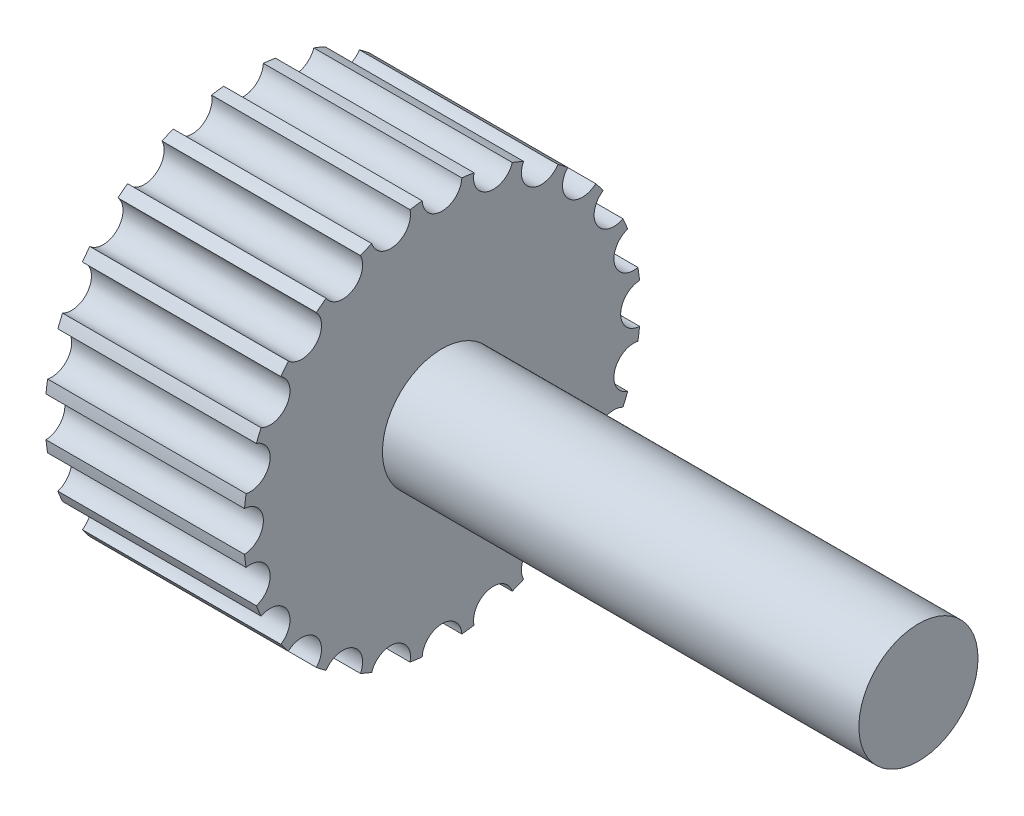
SolidWorks part; units mm, degrees
material "Brass"
ref_plane "Front Plane" through (0, 0, 0) normal (0, 0, 1) x (1, 0, 0)
ref_plane "Top Plane" through (0, 0, 0) normal (0, 1, 0) x (1, 0, 0)
ref_plane "Right Plane" through (0, 0, 0) normal (1, 0, 0) x (0, 0, -1)
sketch "Sketch1" plane through (0, 0, 0) normal (1, 0, 0) x (0, 0, -1)
  circle A0 centre (0, 0) radius 5
  dimension "D1" = 10
extrude "Boss-Extrude1" add sketch "Sketch1" along normal blind 5
sketch "Sketch2" plane through (0, 0, 0) normal (1, 0, 0) x (0, 0, -1)
  circle A0 centre (0, 0) radius 1.5
  dimension "D1" = 3
extrude "Boss-Extrude2" add sketch "Sketch2" along normal blind 17
cosmetic thread "Cosmetic Thread1" parameters "D1"=12, "D2"=0
sketch "Sketch3" plane through (0, 0, 0) normal (1, 0, 0) x (0, 0, -1)
  circle A0 centre (5, 0) radius 0.5
  dimension "D1" = 1
extrude "Cut-Extrude2" cut sketch "Sketch3" against normal blind 5 and the other way blind 5
ref_axis "Axis1" through (-0.85, 0, 0) along (1, 0, 0)
pattern_circular "CirPattern1" count 24 over 360 about axis through (-0.85, 0, 0) along (1, 0, 0) of "Cut-Extrude2"
